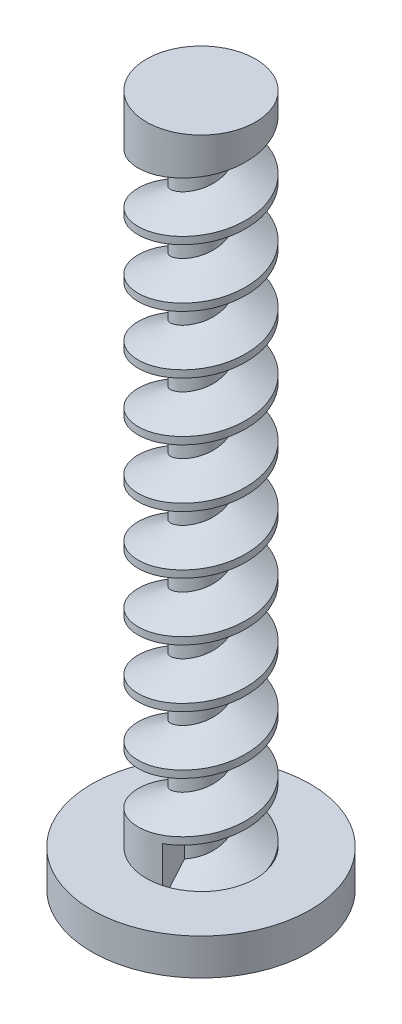
SolidWorks part; units mm, degrees
ref_plane "Front Plane" through (0, 0, 0) normal (0, 0, 1) x (1, 0, 0)
ref_plane "Top Plane" through (0, 0, 0) normal (0, 1, 0) x (1, 0, 0)
ref_plane "Right Plane" through (0, 0, 0) normal (1, 0, 0) x (0, 0, -1)
sketch "Sketch1" plane through (0, 0, 0) normal (0, 1, 0) x (1, 0, 0)
  circle A0 centre (0, 0) radius 1.5
  dimension "D1" = 3
extrude "Boss-Extrude1" add sketch "Sketch1" along normal blind 0.5
sketch "Sketch2" plane through (0, 0.5, 0) normal (0, 1, 0) x (1, 0, 0)
  circle A0 centre (0, 0) radius 0.75
  dimension "D1" = 1.5
extrude "Boss-Extrude2" add sketch "Sketch2" along normal blind 9
thread "Thread1" pitch 0.7937 method cut profile "Thread Profile1" start angle 0, offset 0, length 8.5, pitch 0.7937, diameter 1.5
ref_plane "Plane1" through (-0.75, 9.5, 0) normal (0, 0, 1) x (-1, 0, 0)
sketch "Thread Profile1" plane through (-0.75, 9.5, 0) normal (0, 0, 1) x (-1, 0, 0)
  line L0 (0, 0) -> (0, 0.7937) construction
  line L11 (0, 0) -> (0, 0.6945)
  line L12 (0, 0.6945) -> (-0.4296, 0.4465)
  line L13 (-0.4296, 0.4465) -> (-0.4296, 0.248)
  line L15 (-0.4296, 0.248) -> (0, 0)
  line L17 (-0.4296, 0.3473) -> (0, 0.3473) construction
  point P2 (0, 0)
  dimension "Pitch" = 0.7937
  dimension "Profile_Angle" = 60
  dimension "Profile_Land" = 0.1984
  dimension "Profile_Height" = 0.4296
sketch "Sketch6" plane through (0, 0, 0) normal (0, -1, 0) x (1, 0, 0)
  line L0 (0, -1.085) -> (0, 1.085) construction
  line L1 (-0.086, -1.085) -> (-0.086, 1.085)
  line L2 (0.086, -1.085) -> (0.086, 1.085)
  arc A0 (-0.086, -1.085) -> (0.086, -1.085) centre (0, -1.085) ccw
  arc A1 (0.086, 1.085) -> (-0.086, 1.085) centre (0, 1.085) ccw
  point P2 (0, 0)
  dimension "D1" = 0.172
  dimension "D2" = 2.17
extrude "Cut-Extrude1" cut sketch "Sketch6" against normal blind 0.4 draft 6
